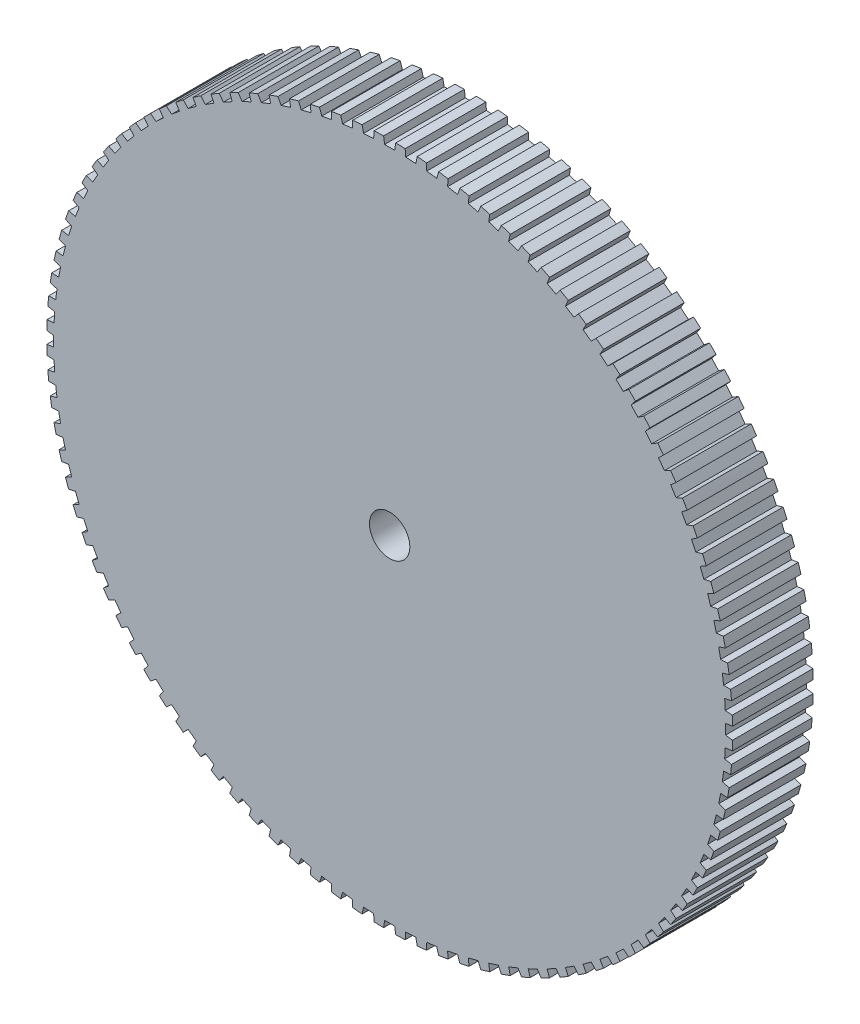
SolidWorks part; units mm, degrees
ref_plane "Front Plane" through (0, 0, 0) normal (0, 0, 1) x (1, 0, 0)
ref_plane "Top Plane" through (0, 0, 0) normal (0, 1, 0) x (1, 0, 0)
ref_plane "Right Plane" through (0, 0, 0) normal (1, 0, 0) x (0, 0, -1)
sketch "Sketch1" plane through (0, 0, 0) normal (0, 0, 1) x (1, 0, 0)
  circle A0 centre (0, 0) radius 37 construction
  circle A2 centre (0, 0) radius 34
  dimension "D1" = 74
  dimension "rubberthk" = 3
extrude "Boss-Extrude1" add sketch "Sketch1" along normal blind 8
sketch "Sketch4" plane through (0, 0, 0) normal (0, 0, -1) x (-1, 0, 0)
  circle A0 centre (0, 0) radius 4.85
  dimension "D1" = 9.7
extrude "Boss-Extrude2" add sketch "Sketch4" along normal blind 8
sketch "Sketch2" plane through (0, 0, 8) normal (0, 0, 1) x (1, 0, 0)
  circle A0 centre (0, 0) radius 4
  dimension "D1" = 8
extrude "Cut-Extrude1" cut sketch "Sketch2" against normal blind 4.35
sketch "Sketch5" plane through (0, 0, 3.65) normal (0, 0, 1) x (1, 0, 0)
  circle A0 centre (0, 0) radius 2
  dimension "D1" = 4
extrude "Cut-Extrude2" cut sketch "Sketch5" against normal offset from surface (4.15 mm away) 7.5 up to face at (-4.85, 0, -8)
sketch "Sketch6" plane through (0, 0, -8) normal (0, 0, -1) x (-1, 0, 0)
  line L0 (2.0785, 1.95) -> (-2.0785, 1.95)
  line L1 (-2.0785, -1.95) -> (2.0785, -1.95)
  arc A0 (2.0785, -1.95) -> (2.0785, 1.95) centre (0, 0) ccw
  arc A1 (-2.0785, 1.95) -> (-2.0785, -1.95) centre (0, 0) ccw
  dimension "D2" = 5.7
  dimension "D1" = 3.9
extrude "Cut-Extrude3" cut sketch "Sketch6" against normal up to surface (7.5 mm away) up to face at (-2, 0, -0.5)
sketch "Sketch7" plane through (0, 0, 8) normal (0, 0, 1) x (1, 0, 0)
  line L0 (-0.6, 33.9947) -> (-0.5, 33.31)
  line L1 (-0.5, 33.31) -> (0.5, 33.31)
  line L2 (0.5, 33.31) -> (0.6, 33.9947)
  line L3 (0, 0) -> (-0.6, 33.9947) construction
  line L4 (0, 0) -> (0.6, 33.9947) construction
  circle A0 centre (0, 0) radius 34 construction
  arc A1 (0.6, 33.9947) -> (-0.6, 33.9947) centre (0, 0) ccw
  point P8 (0, 33.31)
  dimension "D1" = 1
  dimension "D2" = 1.2
  dimension "D3" = 0.69
extrude "Cut-Extrude4" cut sketch "Sketch7" against normal through all
pattern_circular "CirPattern1" count 100 over 360 about axis through (0, 0, 8) along (0, 0, -1) of "Cut-Extrude4"
sketch "Sketch8" plane through (0, 0, 3.65) normal (0, 0, 1) x (1, 0, 0)
  circle A0 centre (0, 0) radius 2 construction
  circle A1 centre (0, 0) radius 4
  circle A2 centre (0, 0) radius 4
  circle A3 centre (0, 0) radius 2
  dimension "D1" = 0
extrude "ReverseCountersink" add sketch "Sketch8" along normal up to surface (4.35 mm away) up to face at (0, 0, 8)
equation "\"width\"= 24"
equation "\"thk\"= 3"
equation "\"holesize\"= 4.2"
equation "\"holedistance\"= ( 20 + 12 ) / 2"
equation "\"threaded_hole\"= 3.9"
equation "\"fillet_radius\"= 2"
equation "\"ground_clearance\"= 25"
equation "\"tire_thk\"= 3"
equation "\"innerwheel_diam\" = \"wheel_diam\"-2*\"tire_thk\""
equation "\"innerwheel_thk\"= 8"
equation "\"wheel_diam\"= 2*(\"width\"/2+\"ground_clearance\")"
equation "\"D1@Sketch1\"=\"wheel_diam\""
equation "\"rubberthk@Sketch1\"=\"tire_thk\""
equation "\"D1@Boss-Extrude1\"=\"innerwheel_thk\""
equation "\"coloursensor_holesize\"= 2.65"
equation "\"hole_to_edge\" = 4"
